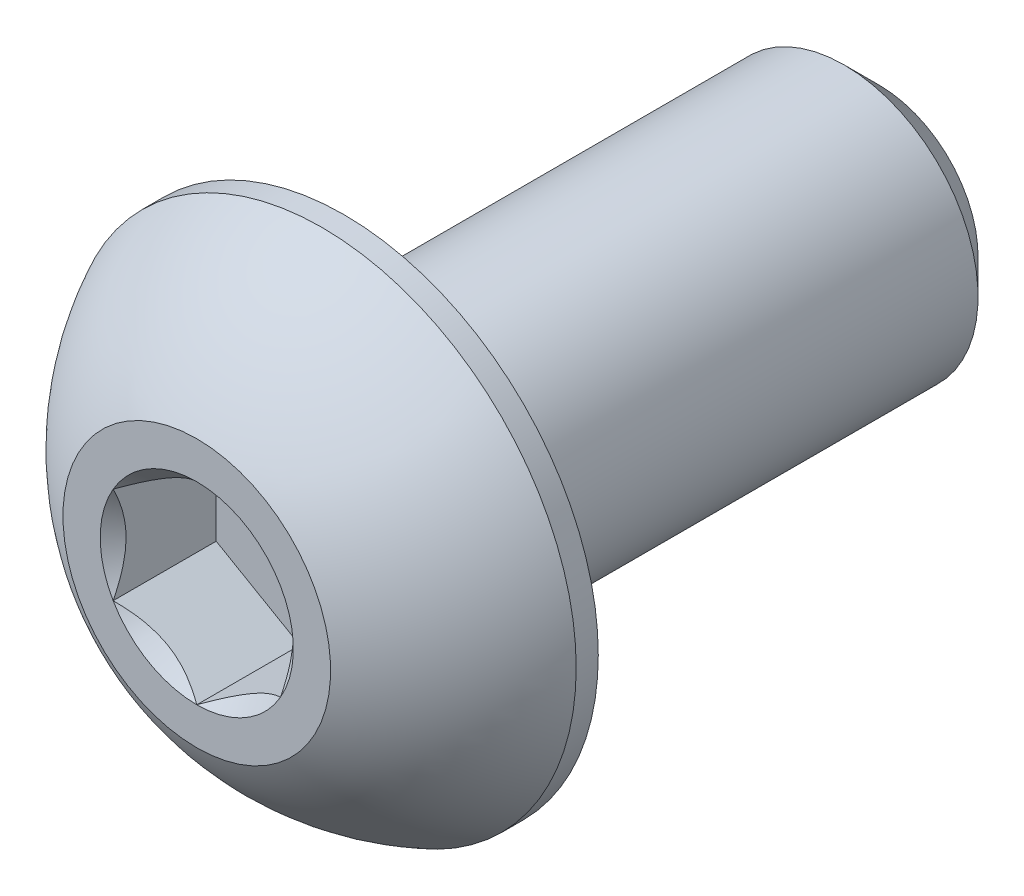
SolidWorks part; units mm, degrees
ref_plane "Front" through (0, 0, 0) normal (0, 0, 1) x (1, 0, 0)
ref_plane "Top" through (0, 0, 0) normal (0, 1, 0) x (1, 0, 0)
ref_plane "Right" through (0, 0, 0) normal (1, 0, 0) x (0, 0, -1)
sketch "Sketch1" plane through (0, 0, 0) normal (1, 0, 0) x (0, 0, -1)
  line L2 (2.2, 2) -> (10.2, 2)
  line L3 (10.2, 2) -> (10.2, 0)
  line L4 (10.2, 0) -> (2.2, 0)
  line L6 (1.87, 3.8) -> (2.2, 3.8) construction
  line L7 (10.2, 2) -> (10.2, -2) construction
  line L8 (0, 0) -> (2.2, 0) construction
  line L9 (2.2, 3.8) -> (2.2, -3.8) construction
  line L11 (2.2, 2) -> (2.2, 0)
  line L13 (0, 1.25) -> (0, -1.25) construction
  line L14 (0, 1.25) -> (0, 2) construction
  arc A3 (0, 2) -> (1.87, 3.8) centre (3.7264, 0) cw construction
  dimension "D1" = 0.33
revolve "Revolve1" add sketch "Sketch1" angle 360 mid plane about L4
sketch "Sketch3" plane through (0, 0, -10.2) normal (0, 0, -1) x (-1, 0, 0)
  circle A0 centre (0, 0) radius 2
curve "Helix/Spiral1" pitch 0.7 height 8.7 turns 12.4286
chamfer "Chamfer1" distance 0.525 angle 45 1 edges at (0, 2, -10.2)
sketch "Sketch7" plane through (0, 0, 0) normal (1, 0, 0) x (0, 0, -1)
  line L6 (1.87, 3.8) -> (2.2, 3.8) construction
  line L8 (0, 0) -> (2.2, 0) construction
  line L11 (2.2, 3.8) -> (2.2, -3.8) construction
  line L12 (1.87, 3.8) -> (2.2, 3.8)
  line L13 (0, 0) -> (2.2, 0)
  line L14 (0, 1.25) -> (0, -1.25) construction
  line L15 (2.2, 3.8) -> (2.2, 0)
  line L16 (0, 2) -> (0, 0)
  arc A2 (1.87, 3.8) -> (0, 2) centre (3.7264, 0) ccw construction
  arc A3 (1.87, 3.8) -> (0, 2) centre (3.7264, 0) ccw
revolve "Revolve2" add sketch "Sketch7" angle 360 mid plane about L13
sketch "Sketch5" plane through (0, 0, 0) normal (0, 0, 1) x (1, 0, 0)
  line L1 (1.25, -0.7217) -> (1.25, 0.7217)
  line L2 (1.25, 0.7217) -> (0, 1.4434)
  line L3 (0, 1.4434) -> (-1.25, 0.7217)
  line L4 (-1.25, 0.7217) -> (-1.25, -0.7217)
  line L5 (-1.25, -0.7217) -> (0, -1.4434)
  line L6 (0, -1.4434) -> (1.25, -0.7217)
  circle A0 centre (0, 0) radius 1.25 construction
extrude "Cut-Extrude2" cut sketch "Sketch5" against normal blind 1.54
sketch "Sketch6" plane through (0, 0, 0) normal (0, 0, 1) x (1, 0, 0)
  circle A0 centre (0, 0) radius 1.4434
extrude "Cut-Extrude3" cut sketch "Sketch6" against normal blind 1.54 draft 45
sketch "Sketch2" plane through (0, 0, 0) normal (1, 0, 0) x (0, 0, -1)
  line L0 (9.675, 2) -> (10.2875, 2)
  line L1 (10.2875, 2) -> (10.025, 1.5453)
  line L2 (10.025, 1.5453) -> (9.9375, 1.5453)
  line L3 (9.9375, 1.5453) -> (9.675, 2)
  line L4 (9.8063, 1.7727) -> (10.1562, 1.7727) construction
  dimension "D1" = 60
  dimension "D2" = 0.0875
  dimension "D3" = 0.35
sweep "Cut-Sweep1" [suppressed] cut profiles "Sketch2" path "Helix/Spiral1"
sketch "Sketch10" plane through (0, 0, 0) normal (1, 0, 0) x (0, 0, -1)
  line L0 (10.2, 2) -> (10.2, -2) construction
  point P0 (9.15, -2)
  dimension "D1" = 1.05
ref_axis "Center Axis 1" through (0, 0, -8.1113) along (0, 0, 1)
ref_plane "Contact Plane 1" through (0, 0, -2.2) normal (0, 0, -1) x (-1, 0, 0)
ref_plane "Contact Plane 2" through (0, 0, 0) normal (0, 0, 1) x (1, 0, 0)
equation "\"D3@Helix/Spiral1\" = \"Lg@Sketch1\" + \"D4@Helix/Spiral1\""
equation "\"D2@Sketch2\" = \"D4@Helix/Spiral1\" * .125"
equation "\"D3@Sketch2\" = \"D4@Helix/Spiral1\" * .5"
equation "\"D1@Chamfer1\" = \"D4@Helix/Spiral1\" * .75"
equation "\"D1@Cut-Extrude2\" = \"Head Ht@Sketch1\" * .7"
equation "\"D1@Sketch1\" = \"Head Ht@Sketch1\" * .15"
equation "\"D1@Sketch10\" = \"D4@Helix/Spiral1\" * 1.5"
equation "\"D1@Cut-Extrude3\" = \"D1@Cut-Extrude2\""
